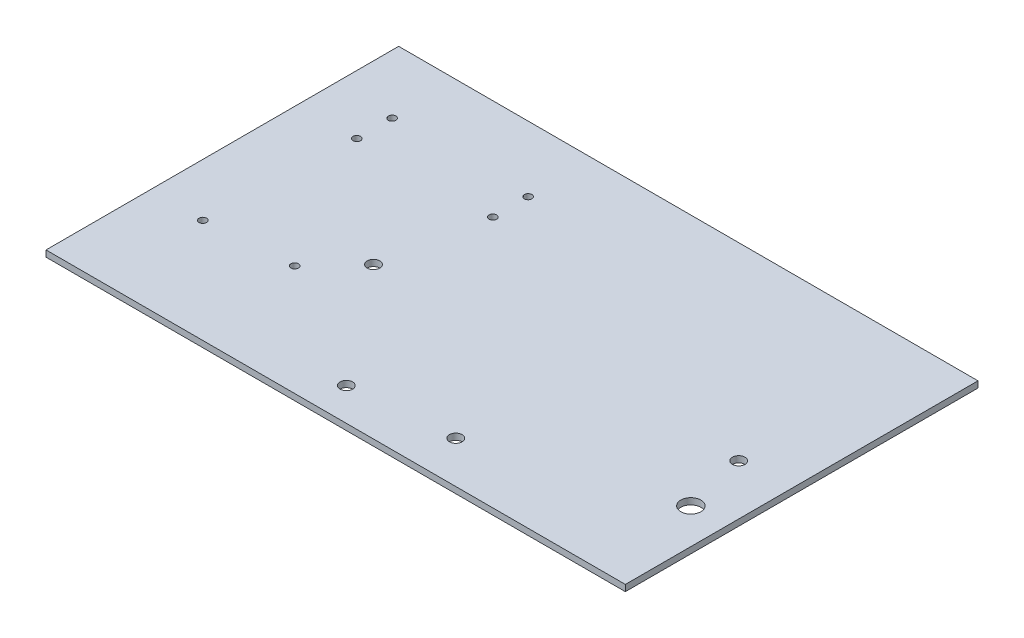
SolidWorks part; units mm, degrees
ref_plane "Front Plane" through (0, 0, 0) normal (0, 0, 1) x (1, 0, 0)
ref_plane "Top Plane" through (0, 0, 0) normal (0, 1, 0) x (1, 0, 0)
ref_plane "Right Plane" through (0, 0, 0) normal (1, 0, 0) x (0, 0, -1)
sketch "Sketch1" plane through (0, 0, 0) normal (0, 1, 0) x (1, 0, 0)
  line L1 (-158.75, 88.9) -> (158.75, 88.9)
  line L2 (-158.75, 88.9) -> (-158.75, -88.9)
  line L3 (-158.75, -88.9) -> (158.75, -88.9)
  line L4 (158.75, 88.9) -> (158.75, -88.9)
  line L5 (-158.75, 88.9) -> (158.75, -88.9) construction
  line L6 (-158.75, -88.9) -> (158.75, 88.9) construction
  circle A0 centre (-69.85, -12.7) radius 3.175
  circle A1 centre (107.95, -6.35) radius 3.175
  circle A4 centre (-129.032, 55.88) radius 1.905
  circle A5 centre (-60.452, 55.88) radius 1.905
  circle A7 centre (-129.032, 38.1) radius 1.905
  circle A8 centre (-60.452, 38.1) radius 1.905
  point P0 (0, 0)
  dimension "D3" = 6.35
  dimension "D4" = 6.35
  dimension "D14" = 3.81
  dimension "D17" = 17.78
  dimension "D1" = 317.5
  dimension "D2" = 177.8
  dimension "D5" = 88.9
  dimension "D6" = 266.7
  dimension "D7" = 95.25
  dimension "D8" = 76.2
  dimension "D13" = 29.718
  dimension "D15" = 68.58
  dimension "D16" = 127
extrude "Boss-Extrude1" add sketch "Sketch1" along normal blind 3.175
sketch "Sketch2" plane through (0, 3.175, 0) normal (0, 1, 0) x (1, 0, 0)
  line L0 (-158.75, 88.9) -> (-158.75, -88.9) construction
  line L1 (-158.75, -88.9) -> (158.75, -88.9) construction
  circle A0 centre (-89.0817, -33.177) radius 1.905
  circle A1 centre (-132.1376, -36.4483) radius 1.905
  dimension "D1" = 3.81
  dimension "D2" = 69.6683
  dimension "D3" = 52.4517
  dimension "D4" = 55.723
  dimension "D5" = 43.18
extrude "Cut-Extrude1" cut sketch "Sketch2" against normal through all
sketch "Sketch3" plane through (0, 0, 0) normal (0, -1, 0) x (-1, 0, 0)
  line L0 (158.75, -88.9) -> (-158.75, -88.9) construction
  line L1 (158.75, 88.9) -> (158.75, -88.9) construction
  circle A0 centre (23.8295, -72.39) radius 3.175
  circle A1 centre (-26.7643, -67.818) radius 3.175
  dimension "D1" = 6.35
  dimension "D2" = 4.572
  dimension "D3" = 16.51
  dimension "D4" = 185.5143
  dimension "D5" = 50.8
extrude "Cut-Extrude2" cut sketch "Sketch3" against normal through all
sketch "Sketch4" plane through (0, 3.175, 0) normal (0, 1, 0) x (1, 0, 0)
  line L0 (-158.75, -88.9) -> (158.75, -88.9) construction
  line L1 (158.75, 88.9) -> (133.35, 88.9)
  line L2 (158.75, 88.9) -> (158.75, -88.9)
  line L3 (158.75, -88.9) -> (133.35, -88.9)
  line L4 (133.35, 88.9) -> (133.35, -88.9)
  dimension "D1" = 25.4
extrude "Cut-Extrude3" cut sketch "Sketch4" against normal through all
sketch "Sketch5" plane through (0, 3.175, 0) normal (0, 1, 0) x (1, 0, 0)
  line L0 (133.35, 88.9) -> (-158.75, 88.9) construction
  line L1 (133.35, 88.9) -> (133.35, -88.9) construction
  circle A0 centre (115.57, -38.1) radius 5.08
  dimension "D3" = 10.16
  dimension "D1" = 127
  dimension "D2" = 17.78
extrude "Cut-Extrude4" cut sketch "Sketch5" against normal through all
